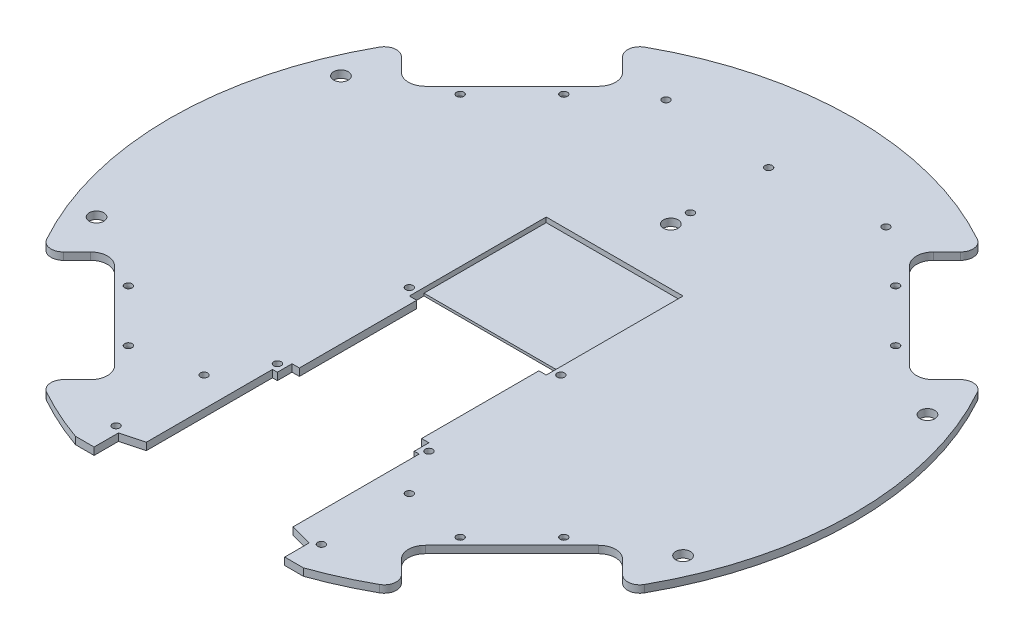
SolidWorks part; units mm, degrees
material "1060 Alloy"
ref_plane "Front Plane" through (0, 0, 0) normal (0, 0, 1) x (1, 0, 0)
ref_plane "Top Plane" through (0, 0, 0) normal (0, 1, 0) x (1, 0, 0)
ref_plane "Right Plane" through (0, 0, 0) normal (1, 0, 0) x (0, 0, -1)
sketch "Sketch1" plane through (0, 0, 0) normal (0, 1, 0) x (1, 0, 0)
  circle A0 centre (0, 0) radius 140
  dimension "D1" = 280
extrude "Boss-Extrude1" add sketch "Sketch1" along normal blind 3
sketch "Sketch7" plane through (0, 3, 0) normal (0, 1, 0) x (1, 0, 0)
  line L0 (-99.0303, -63.6043) -> (-63.6043, -99.0303)
  line L1 (-108.8591, -63.6043) -> (-121.6224, -76.3675)
  line L2 (-63.6043, -108.8591) -> (-76.3675, -121.6224)
  line L3 (-121.6224, -76.3675) -> (-76.3675, -121.6224)
  line L4 (0, 0) -> (-98.9949, -98.9949) construction
  line L7 (0, 0) -> (0, 130) construction
  circle A0 centre (0, 0) radius 140 construction
  arc A1 (-108.8591, -63.6043) -> (-99.0303, -63.6043) centre (-103.9447, -68.5186) cw
  arc A2 (-63.6043, -99.0303) -> (-63.6043, -108.8591) centre (-68.5186, -103.9447) cw
  dimension "D4" = 6.95
  dimension "D1" = 115
  dimension "D2" = 64
  dimension "D3" = 135
extrude "Cut-Extrude4" cut sketch "Sketch7" against normal up to next
sketch "Sketch9" plane through (0, 3, 0) normal (0, 1, 0) x (1, 0, 0)
  line L1 (-63.6043, -99.0303) -> (-99.0303, -63.6043) construction
  line L4 (-108.8591, -63.6043) -> (-119.0017, -73.7469) construction
  circle A0 centre (-89.0955, -67.8823) radius 1.5
  circle A1 centre (-67.8823, -89.0955) radius 1.5
  dimension "D4" = 3
  dimension "D1" = 4
  dimension "D2" = 30
  dimension "D3" = 17
  dimension "D5" = 4
extrude "Cut-Extrude6" cut sketch "Sketch9" against normal up to next
fillet "Fillet1" radius 5 2 edges at (-73.7469, 1.5, 119.0017) (-119.0017, 1.5, 73.7469)
pattern_circular "CirPattern1" count 4 over 360 about axis through (0, 3, 0) along (0, 1, 0) of "Cut-Extrude4", "Fillet1", "Cut-Extrude6"
sketch "Sketch2" plane through (0, 3, 0) normal (0, 1, 0) x (1, 0, 0)
  line L0 (-46.6476, -132) -> (-39, -132)
  line L1 (-30, -119.5885) -> (-30, -68)
  line L2 (-28, -8) -> (28, -8)
  line L3 (30, -68) -> (30, -119.5885)
  line L4 (39, -132) -> (46.6476, -132)
  line L5 (46.6476, -132) -> (46.6476, -140)
  line L6 (46.6476, -140) -> (-46.6476, -140)
  line L7 (-46.6476, -140) -> (-46.6476, -132)
  line L8 (-28, -62) -> (-28, -68)
  line L9 (-28, -68) -> (-30, -68)
  line L10 (28, -62) -> (28, -68)
  line L11 (28, -68) -> (30, -68)
  line L12 (-28, -62) -> (-25, -62)
  line L13 (-25, -62) -> (-25, -14)
  line L14 (-25, -14) -> (-28, -14)
  line L15 (-28, -14) -> (-28, -8)
  line L16 (28, -8) -> (28, -14)
  line L17 (28, -14) -> (25, -14)
  line L18 (25, -14) -> (25, -62)
  line L19 (25, -62) -> (28, -62)
  line L20 (-39, -132) -> (-39, -122)
  line L21 (-39, -122) -> (-30, -119.5885)
  line L22 (39, -132) -> (39, -122)
  line L23 (39, -122) -> (30, -119.5885)
  circle A0 centre (0, 0) radius 140 construction
  dimension "D8" = 3
  dimension "D5" = 60
  dimension "D6" = 56
  dimension "D1" = 8
  dimension "D2" = 124
  dimension "D3" = 60
  dimension "D4" = 16.6476
  dimension "D7" = 6
  dimension "D9" = 78
  dimension "D10" = 10
  dimension "D11" = 105
extrude "Cut-Extrude1" cut sketch "Sketch2" against normal up to next
fillet "Fillet3" radius 1.5 8 edges at (67.8823, 0, 90.5955) (89.0955, 0, 69.3823) (89.0955, 0, -66.3823) (67.8823, 0, -87.5955) (-67.8823, 0, -87.5955) (-89.0955, 0, -66.3823) (-67.8823, 0, 90.5955) (-89.0955, 0, 69.3823)
sketch "Sketch10" plane through (0, 3, 0) normal (0, 1, 0) x (1, 0, 0)
  circle A0 centre (-31, -65) radius 1.5
  circle A1 centre (31, -65) radius 1.5
  circle A2 centre (-31, -11) radius 1.5
  circle A3 centre (31, -11) radius 1.5
  dimension "D3" = 3
  dimension "D1" = 31
  dimension "D2" = 62
  dimension "D4" = 65
  dimension "D5" = 54
extrude "Cut-Extrude7" cut sketch "Sketch10" against normal up to next
sketch "Sketch13" plane through (0, 3, 0) normal (0, 1, 0) x (1, 0, 0)
  line L1 (-39, -132) -> (-46.6476, -132) construction
  circle A0 centre (-42, -84) radius 1.5
  circle A1 centre (-42, -120) radius 1.5
  circle A2 centre (42, -120) radius 1.5
  circle A3 centre (42, -84) radius 1.5
  dimension "D1" = 3
  dimension "D2" = 12
  dimension "D3" = 36
  dimension "D4" = 42
  dimension "D5" = 42
extrude "Cut-Extrude9" cut sketch "Sketch13" against normal up to next
sketch "Sketch16" plane through (0, 3, 0) normal (0, 1, 0) x (1, 0, 0)
  circle A0 centre (0, 73) radius 1.5
  circle A1 centre (-45, 108) radius 1.5
  circle A2 centre (45, 108) radius 1.5
  circle A3 centre (0, 105) radius 1.5
  circle A4 centre (0, 65) radius 3
  dimension "D2" = 3
  dimension "D5" = 6
  dimension "D1" = 73
  dimension "D3" = 108
  dimension "D4" = 90
  dimension "D6" = 32
  dimension "D7" = 65
extrude "Cut-Extrude12" cut sketch "Sketch16" against normal up to next
sketch "Sketch17" plane through (0, 3, 0) normal (0, 1, 0) x (1, 0, 0)
  circle A0 centre (-120, 50) radius 3
  circle A1 centre (-120, -50) radius 3
  circle A2 centre (120, 50) radius 3
  circle A3 centre (120, -50) radius 3
  dimension "D1" = 6
  dimension "D2" = 50
  dimension "D3" = 50
  dimension "D4" = 120
  dimension "D5" = 120
extrude "Cut-Extrude13" cut sketch "Sketch17" against normal up to next
sketch "Sketch18" plane through (0, 3, 0) normal (0, 1, 0) x (1, 0, 0)
  line L0 (-28, -8) -> (-28, -14) construction
  line L1 (-28, -8) -> (28, -8)
  line L2 (-28, -8) -> (-28, 42)
  line L3 (-28, 42) -> (28, 42)
  line L4 (28, -8) -> (28, 42)
  line L5 (28, -8) -> (-28, -8) construction
  line L6 (28, -8) -> (-28, -8) construction
  dimension "D1" = 50
extrude "Cut-Extrude14" cut sketch "Sketch18" against normal blind 2
